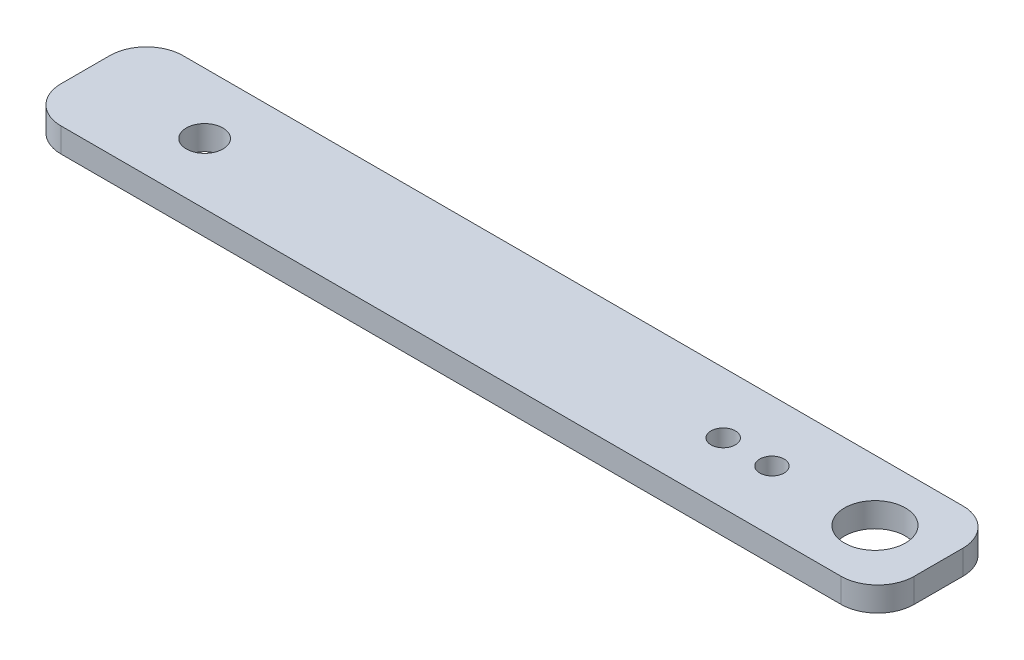
SolidWorks part; units mm, degrees
ref_plane "Front Plane" through (0, 0, 0) normal (0, 0, 1) x (1, 0, 0)
ref_plane "Top Plane" through (0, 0, 0) normal (0, 1, 0) x (1, 0, 0)
ref_plane "Right Plane" through (0, 0, 0) normal (1, 0, 0) x (0, 0, -1)
sketch "Sketch1" plane through (0, 0, 0) normal (0, 1, 0) x (1, 0, 0)
  line L1 (-35, 5) -> (35, 5)
  line L2 (-35, 5) -> (-35, -5)
  line L3 (-35, -5) -> (35, -5)
  line L4 (35, 5) -> (35, -5)
  line L5 (-35, 5) -> (35, -5) construction
  line L6 (-35, -5) -> (35, 5) construction
  point P0 (0, 0)
  dimension "D1" = 10
  dimension "D2" = 70
extrude "Boss-Extrude1" add sketch "Sketch1" along normal blind 2
hole_wizard "Ø5.0mm Dowel Hole1" positions "Sketch5" profile "Sketch6" hole size "Ø5.0" standard "ISO" end condition through all
sketch "Sketch5" plane through (0, 2, 0) normal (0, 1, 0) x (1, 0, 0)
  point P0 (29.7797, 0)
  point P8 (29.7797, 0)
sketch "Sketch6" plane through (29.7797, 2, 0) normal (1, 0, 0) x (0, 0, 1)
  line L0 (0, 0) -> (0, 2)
  line L1 (0, 2) -> (2.5, 2)
  line L2 (2.5, 2) -> (2.5, 0)
  line L5 (2.5, 0) -> (0, 0)
  line L11 (0, -6.35) -> (0, 107.95) construction
  dimension "Thru Hole Dia." = 5
  dimension "Thru Hole Depth" = 2
hole_wizard "Ø3.0mm Dowel Hole1" positions "Sketch3" profile "Sketch4" hole size "Ø3.0" standard "ISO" end condition through all
sketch "Sketch3" plane through (0, 2, 0) normal (0, 1, 0) x (1, 0, 0)
  circle A0 centre (29.7797, 0) radius 2.5 construction
  point P0 (-25.2203, 0)
  dimension "D1" = 55
sketch "Sketch4" plane through (-25.2203, 2, 0) normal (1, 0, 0) x (0, 0, 1)
  line L0 (0, 0) -> (0, 2)
  line L1 (0, 2) -> (1.5, 2)
  line L2 (1.5, 2) -> (1.5, 0)
  line L5 (1.5, 0) -> (0, 0)
  line L11 (0, -6.35) -> (0, 107.95) construction
  dimension "Thru Hole Dia." = 3
  dimension "Thru Hole Depth" = 2
sketch "Sketch2" plane through (0, 2, 0) normal (0, 1, 0) x (1, 0, 0)
  line L0 (29.7797, 5) -> (29.7797, -5) construction
  line L1 (-35, -5) -> (35, -5) construction
  line L3 (35, 0) -> (-35, 0) construction
  line L4 (35, -5) -> (35, 5) construction
  line L5 (-35, 5) -> (-35, -5) construction
  circle A3 centre (21.3297, 0) radius 1
  circle A4 centre (17.3297, 0) radius 1
  point P4 (0, 0)
  point P5 (24.4139, 0)
  point P10 (29.7797, 0)
  point P11 (0, 0)
  point P12 (24.4139, -5)
  point P19 (0, 0)
  dimension "D1" = 2
  dimension "D2" = 8.45
  dimension "D3" = 4
extrude "Cut-Extrude1" cut sketch "Sketch2" against normal blind 3
fillet "Fillet1" radius 3 4 edges at (35, 1, 5) (35, 1, -5) (-35, 1, -5) (-35, 1, 5)
equation "\"globalength1\"=55"
